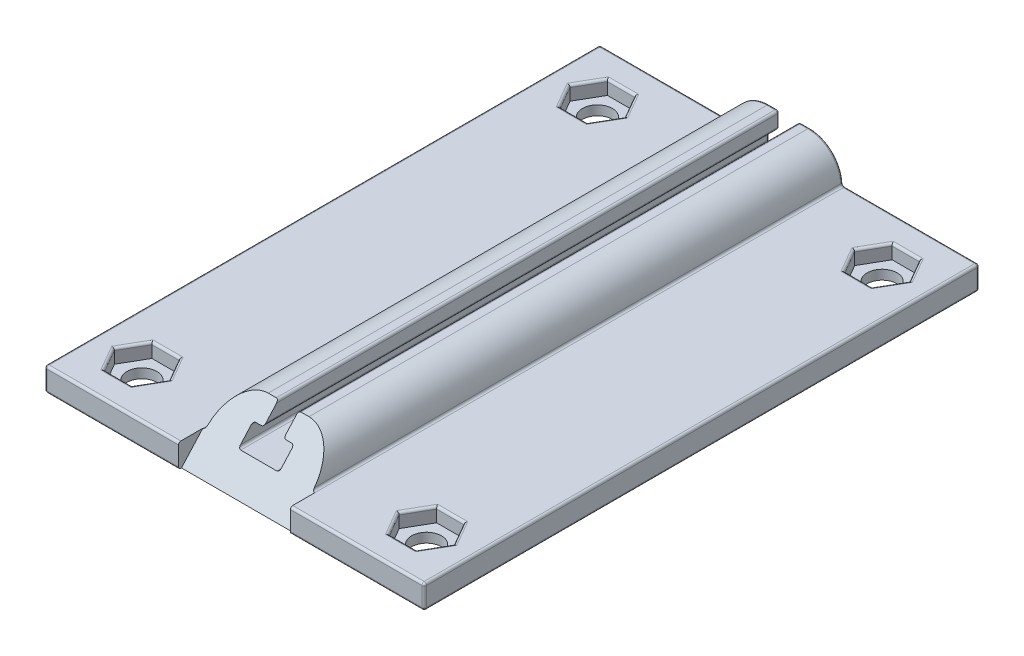
SolidWorks part; units mm, degrees
ref_plane "Front Plane" through (0, 0, 0) normal (0, 0, 1) x (1, 0, 0)
ref_plane "Top Plane" through (0, 0, 0) normal (0, 1, 0) x (1, 0, 0)
ref_plane "Right Plane" through (0, 0, 0) normal (1, 0, 0) x (0, 0, -1)
sketch "Sketch1" plane through (0, 0, 0) normal (0, 0, 1) x (1, 0, 0)
  line L0 (0, -28.2286) -> (0, 28.2286) construction
  line L1 (-40, -2.5) -> (40, -2.5)
  line L2 (-40, -2.5) -> (-40, 2.5)
  line L3 (-40, 2.5) -> (-11.3, 2.5)
  line L4 (40, -2.5) -> (40, 2.5)
  line L5 (-40, -2.5) -> (40, 2.5) construction
  line L6 (-40, 2.5) -> (40, -2.5) construction
  line L7 (-4.3, 2.5) -> (4.3, 2.5)
  line L8 (0.2, 2.5) -> (-4.3, 2.5) construction
  line L9 (0.2, 2.5) -> (0.2, 6) construction
  line L10 (0.2, 6) -> (-4.3, 6) construction
  line L12 (0.2, 6) -> (-2.1, 6) construction
  line L13 (0.2, 6) -> (0.2, 16.858) construction
  line L14 (0.2, 16.858) -> (-2.1, 16.858) construction
  line L15 (-2.1, 6) -> (-2.1, 16.858) construction
  line L16 (-4.3, 6) -> (-2.1, 6)
  line L17 (-4.3, 2.5) -> (-4.3, 6)
  line L18 (-4.3, 9.5) -> (-2.1, 9.5)
  line L19 (-2.1, 6) -> (-2.1, 9.5)
  line L20 (4.3, 2.5) -> (4.3, 6)
  line L21 (2.1, 6) -> (2.1, 9.5)
  line L22 (4.3, 6) -> (2.1, 6)
  line L23 (4.3, 9.5) -> (2.1, 9.5)
  line L24 (11.3, 2.5) -> (40, 2.5)
  arc A0 (-4.3, 9.5) -> (-11.3, 2.5) centre (-4.3, 2.5) ccw
  arc A1 (4.3, 9.5) -> (11.3, 2.5) centre (4.3, 2.5) cw
  point P0 (0, 0)
  point P9 (0, 0)
  dimension "D1" = 80
  dimension "D2" = 5
  dimension "D3" = 3.5
  dimension "D4" = 4.5
  dimension "D5" = 2.3
  dimension "D6" = 3.5
  dimension "D7" = 4.3
  dimension "D8" = 4.2
extrude "Boss-Extrude1" add sketch "Sketch1" along normal blind 58.5 and the other way blind 58.5 contours L7 L20 L22 L21 L23 A1 L24 L4 L1 L2 L3 A0 L18 L19 L16 L17
sketch "Sketch2" plane through (0, -2.5, 0) normal (0, -1, 0) x (1, 0, 0)
  line L0 (0, -58.5) -> (0, -52) construction
  line L2 (-40, -58.5) -> (40, -58.5) construction
  line L3 (0, 58.5) -> (0, 48) construction
  line L4 (-40, 58.5) -> (40, 58.5) construction
  line L5 (0, 48) -> (-30, 48) construction
  circle A0 centre (-30, 48) radius 3.15
  circle A1 centre (30, 48) radius 3.15
  circle A2 centre (30, -48) radius 3.15
  circle A3 centre (-30, -48) radius 3.15
  point P6 (0, 0)
  dimension "D4" = 6.3
  dimension "D1" = 10.5
  dimension "D2" = 6.5
  dimension "D3" = 30
  dimension "D5" = 2
  dimension "D6" = 2
extrude "Cut-Extrude1" cut sketch "Sketch2" against normal blind 58.5
fillet "Fillet1" radius 0.5 50 edges at (40, -2.5, 0) (-40, -2.5, 0) (-4.3, 6, 0) (-2.1, 6, 0) (-2.1, 9.5, 0) (2.1, 9.5, 0) (2.1, 6, 0) (4.3, 6, 0) (4.3, 2.5, 0) (-4.3, 2.5, 0) (-3.2, 6, -58.5) (-2.1, 7.75, -58.5) (-3.2, 9.5, -58.5) (-9.2497, 7.4497, -58.5) (-40, 0, -58.5) (0, -2.5, -58.5) (40, 0, -58.5) (9.2497, 7.4497, -58.5) (3.2, 9.5, -58.5) (2.1, 7.75, -58.5) (3.2, 6, -58.5) (4.3, 4.25, -58.5) (0, 2.5, -58.5) (-4.3, 4.25, -58.5) (0, 2.5, 58.5) (4.3, 4.25, 58.5) (3.2, 6, 58.5) (2.1, 7.75, 58.5) (3.2, 9.5, 58.5) (9.2497, 7.4497, 58.5) (40, 0, 58.5) (0, -2.5, 58.5) (-40, 0, 58.5) (-9.2497, 7.4497, 58.5) (-3.2, 9.5, 58.5) (-2.1, 7.75, 58.5) (-3.2, 6, 58.5) (-4.3, 4.25, 58.5) (-25.65, 2.5, -58.5) (-11.3, 2.5, 0) (-25.65, 2.5, 58.5) (-40, 2.5, 0) (-26.85, 2.5, -48) (-26.85, 2.5, 48) (25.65, 2.5, -58.5) (40, 2.5, 0) (25.65, 2.5, 58.5) (11.3, 2.5, 0) (33.15, 2.5, 48) (33.15, 2.5, -48)
sketch "Sketch3" plane through (0, 2.5, 0) normal (0, 1, 0) x (1, 0, 0)
  line L1 (-24.2265, 48) -> (-27.1132, 53)
  line L2 (-27.1132, 53) -> (-32.8868, 53)
  line L3 (-32.8868, 53) -> (-35.7735, 48)
  line L4 (-35.7735, 48) -> (-32.8868, 43)
  line L5 (-32.8868, 43) -> (-27.1132, 43)
  line L6 (-27.1132, 43) -> (-24.2265, 48)
  line L7 (-24.2265, -48) -> (-27.1132, -43)
  line L8 (-27.1132, -43) -> (-32.8868, -43)
  line L9 (-32.8868, -43) -> (-35.7735, -48)
  line L10 (-35.7735, -48) -> (-32.8868, -53)
  line L11 (-32.8868, -53) -> (-27.1132, -53)
  line L12 (-27.1132, -53) -> (-24.2265, -48)
  circle A0 centre (-30, 48) radius 5 construction
  circle A1 centre (-30, -48) radius 5 construction
  dimension "D1" = 10
  dimension "D2" = 10
extrude "Cut-Extrude2" cut sketch "Sketch3" against normal blind 3
pattern_linear "LPattern1" count 2 spacing 60 along (1, 0, 0) of "Cut-Extrude2"
fillet "Fillet2" radius 0.5 24 edges at (30, 2.5, 43) (25.6699, 2.5, 45.5) (25.6699, 2.5, 50.5) (30, 2.5, 53) (34.3301, 2.5, 50.5) (34.3301, 2.5, 45.5) (30, 2.5, -53) (25.6699, 2.5, -50.5) (25.6699, 2.5, -45.5) (30, 2.5, -43) (34.3301, 2.5, -45.5) (34.3301, 2.5, -50.5) (-30, 2.5, 43) (-34.3301, 2.5, 45.5) (-34.3301, 2.5, 50.5) (-30, 2.5, 53) (-25.6699, 2.5, 50.5) (-25.6699, 2.5, 45.5) (-30, 2.5, -53) (-34.3301, 2.5, -50.5) (-34.3301, 2.5, -45.5) (-30, 2.5, -43) (-25.6699, 2.5, -45.5) (-25.6699, 2.5, -50.5)
sketch "Sketch6" plane through (2.1, 0, 0) normal (-1, 0, 0) x (0, 0, 1)
  line L0 (47.07, 9.5) -> (58.5, -3.2)
  line L2 (58.5, -3.2) -> (58.5, 9.5)
  line L3 (58.5, 9.5) -> (47.07, 9.5)
  line L4 (-58, 9.5) -> (58, 9.5) construction
  line L6 (58.5, 9) -> (58.5, 6.5) construction
  point P2 (53.0366, 9)
  point P3 (58.4477, 9)
  point P4 (58.5187, 9)
  point P6 (53.4644, 9.5)
  point P7 (58.4163, 9)
  point P8 (57.4712, -7.7792)
  point P9 (53.1947, 9)
  point P12 (58.5, -1.9386)
  point P15 (0, 0)
  point P16 (58.5, -2.0497)
  point P17 (58.5, -2.3113)
  point P18 (58.5, 2.0394)
  dimension "D1" = 11.43
  dimension "D2" = 12.7
extrude "Cut-Extrude3" cut sketch "Sketch6" against normal up to vertex (9.6833 mm away) and the other way up to vertex (13.8833 mm away) up to point (11.7833, 2.5, 58) other way up to point (-11.7833, 2.5, 58)
